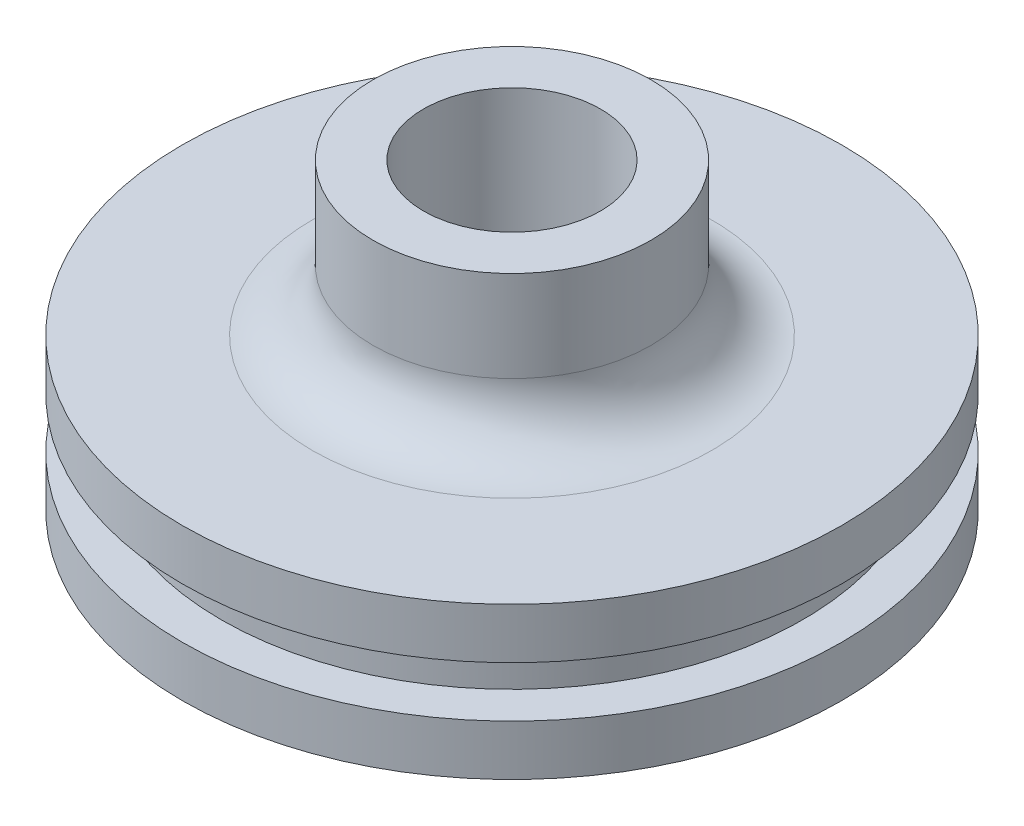
SolidWorks part; units mm, degrees
ref_plane "Front Plane" through (0, 0, 0) normal (0, 0, 1) x (1, 0, 0)
ref_plane "Top Plane" through (0, 0, 0) normal (0, 1, 0) x (1, 0, 0)
ref_plane "Right Plane" through (0, 0, 0) normal (1, 0, 0) x (0, 0, -1)
sketch "Sketch2" plane through (0, 0, 0) normal (0, 0, 1) x (1, 0, 0)
  line L0 (0, 0) -> (0, -9.525) construction
  line L1 (0, 0) -> (-20.701, 0) construction
  line L2 (-20.701, 0) -> (-20.701, -3.175)
  line L3 (-20.701, -3.175) -> (-18.2562, -3.175)
  line L4 (-18.2562, -3.175) -> (-18.2562, -6.35)
  line L5 (-18.2562, -6.35) -> (-20.701, -6.35)
  line L6 (-20.701, -6.35) -> (-20.701, -9.525)
  line L7 (-20.701, -3.175) -> (-20.701, -6.35) construction
  line L8 (-20.701, -9.525) -> (0, -9.525) construction
  line L10 (-5.5563, 9.525) -> (-5.5562, -3.175)
  line L11 (-5.5562, -3.175) -> (-1.5875, -3.175)
  line L12 (-1.5875, -3.175) -> (-1.5875, -9.525)
  line L13 (-1.5875, -9.525) -> (-20.701, -9.525)
  line L14 (-20.701, 0) -> (-12.5413, 0)
  line L15 (-8.7312, 3.81) -> (-8.7313, 9.525)
  line L16 (-8.7313, 9.525) -> (-5.5563, 9.525)
  arc A0 (-8.7312, 3.81) -> (-12.5413, 0) centre (-12.5412, 3.81) cw
  point P17 (-8.7312, 0)
  dimension "D11" = 3.81
  dimension "D1" = 20.701
  dimension "D2" = 18.2562
  dimension "D3" = 3.175
  dimension "D4" = 6.35
  dimension "D5" = 3.175
  dimension "D6" = 1.5875
  dimension "D7" = 3.175
  dimension "D8" = 5.5562
  dimension "D9" = 3.175
  dimension "D10" = 12.7
revolve "base" add sketch "Sketch2" angle 360 about L0
